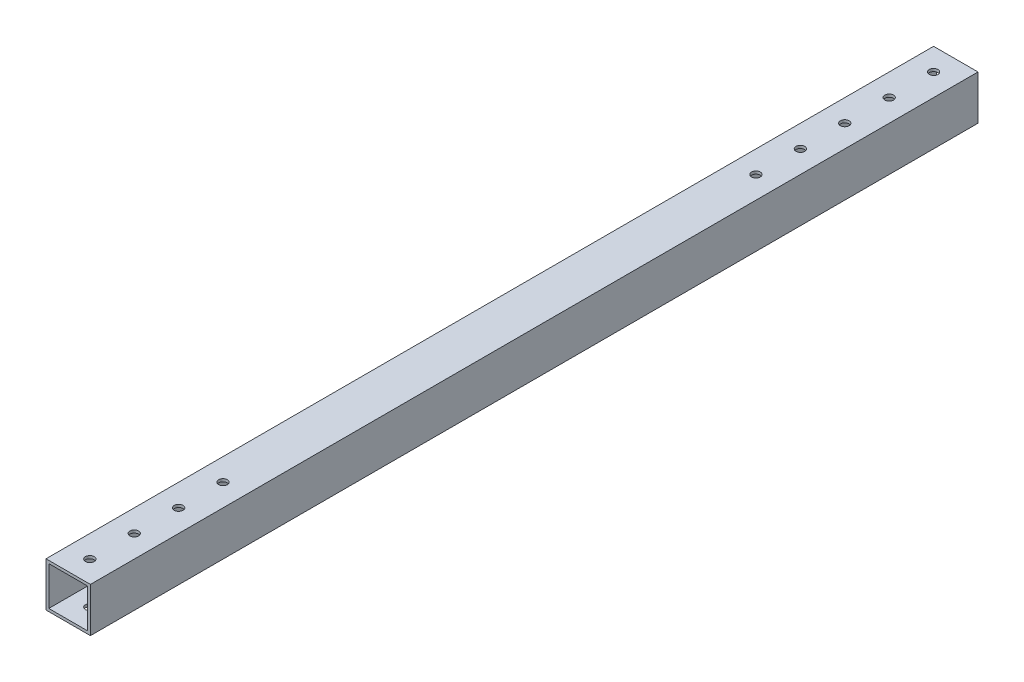
SolidWorks part; units mm, degrees
material "6061-T6 (SS)"
ref_plane "Front Plane" through (0, 0, 0) normal (0, 0, 1) x (1, 0, 0)
ref_plane "Top Plane" through (0, 0, 0) normal (0, 1, 0) x (1, 0, 0)
ref_plane "Right Plane" through (0, 0, 0) normal (1, 0, 0) x (0, 0, -1)
sketch "Sketch1" plane through (0, 0, 0) normal (0, 0, 1) x (1, 0, 0)
  line L1 (-12.7, -12.7) -> (12.7, -12.7)
  line L2 (-12.7, -12.7) -> (-12.7, 12.7)
  line L3 (-12.7, 12.7) -> (12.7, 12.7)
  line L4 (12.7, -12.7) -> (12.7, 12.7)
  line L5 (-12.7, -12.7) -> (12.7, 12.7) construction
  line L6 (-12.7, 12.7) -> (12.7, -12.7) construction
  point P0 (0, 0)
  dimension "D1" = 25.4
  dimension "D2" = 25.4
extrude "Boss-Extrude1" add sketch "Sketch1" along normal mid plane 507.6738
shell "Shell1" thickness 1.5875 removed face at (0, 0, -253.8369) removed face at (0, 0, 253.8369)
sketch "Sketch3" plane through (0, 0, 0) normal (0, 1, 0) x (1, 0, 0)
  line L0 (12.7, 253.8369) -> (-12.7, 253.8369) construction
  circle A0 centre (0, 241.1369) radius 2.4892
  circle A1 centre (0, 215.7369) radius 2.4892
  circle A2 centre (0, 190.3369) radius 2.4892
  circle A3 centre (0, 164.9369) radius 2.4892
  circle A4 centre (0, 139.5369) radius 2.4892
  circle A5 centre (0, 114.1369) radius 2.4892 construction
  circle A6 centre (0, 88.7369) radius 2.4892 construction
  circle A7 centre (0, 63.3369) radius 2.4892 construction
  circle A8 centre (0, 37.9369) radius 2.4892 construction
  circle A9 centre (0, 12.5369) radius 2.4892 construction
  circle A10 centre (0, -12.8631) radius 2.4892 construction
  circle A11 centre (0, -38.2631) radius 2.4892 construction
  circle A12 centre (0, -63.6631) radius 2.4892 construction
  circle A13 centre (0, -89.0631) radius 2.4892 construction
  circle A14 centre (0, -114.4631) radius 2.4892 construction
  circle A15 centre (0, -139.8631) radius 2.4892 construction
  circle A16 centre (0, -165.2631) radius 2.4892
  circle A17 centre (0, -190.6631) radius 2.4892
  circle A18 centre (0, -216.0631) radius 2.4892
  circle A19 centre (0, -241.4631) radius 2.4892
  point P4 (0, 253.8369)
  dimension "D1" = 4.9784
  dimension "D2" = 12.7
  dimension "D4" = 25.4
  dimension "D3" = 20
extrude "Cut-Extrude1" cut sketch "Sketch3" against normal through all both and the other way through all
